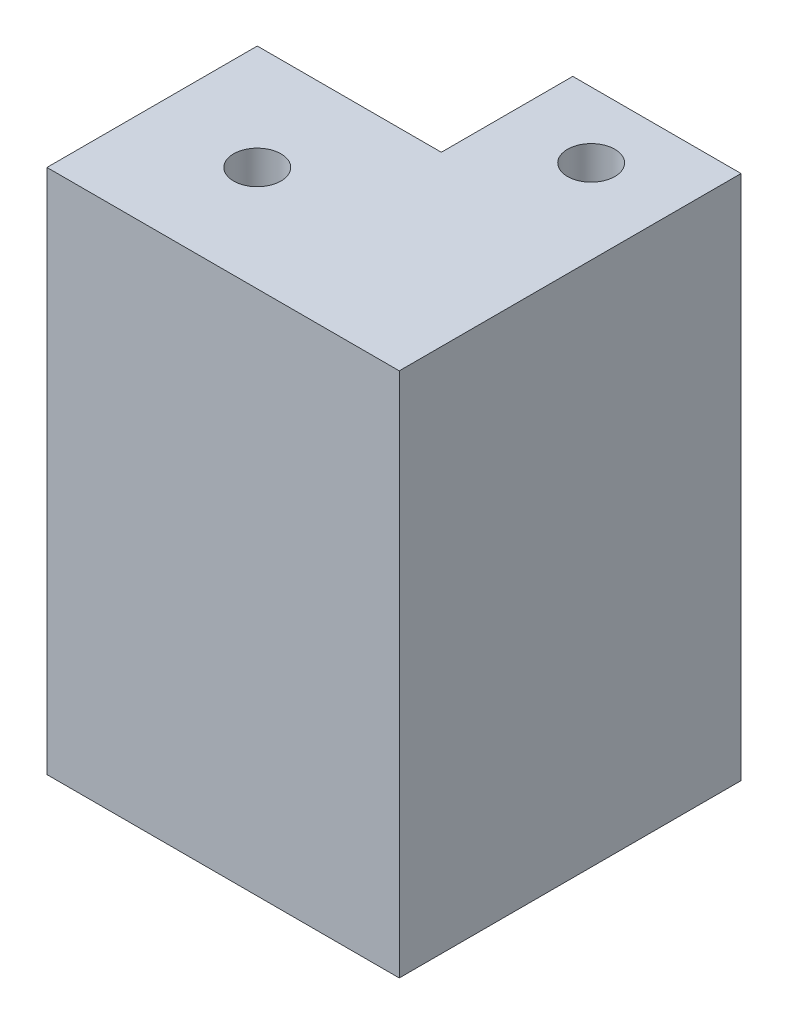
SolidWorks part; units mm, degrees
ref_plane "Front Plane" through (0, 0, 0) normal (0, 0, 1) x (1, 0, 0)
ref_plane "Top Plane" through (0, 0, 0) normal (0, 1, 0) x (1, 0, 0)
ref_plane "Right Plane" through (0, 0, 0) normal (1, 0, 0) x (0, 0, -1)
sketch "Sketch1" plane through (0, 0, 0) normal (0, 1, 0) x (1, 0, 0)
  line L19 (0, -40) -> (0, 0) construction
  line L24 (-25, 0) -> (-5, -40) construction
  line L25 (0, 25) -> (-25, 25) construction
  line L26 (-25, 25) -> (-25, 0) construction
  line L27 (0, 25) -> (32, 0) construction
  line L28 (32, 0) -> (0, 0) construction
  line L29 (-35, 0) -> (0, 0)
  line L30 (-35, -40) -> (-35, 0)
  line L31 (32, -40) -> (-35, -40)
  line L32 (32, 25) -> (32, -40)
  line L33 (0, 25) -> (32, 25)
  line L34 (0, 0) -> (0, 25)
  line L35 (-5, 5) -> (-5, -40) construction
  line L36 (-25, 25) -> (-5, 25) construction
  line L37 (-25, 25) -> (-25, 5) construction
  line L38 (-25, 5) -> (-5, 5) construction
  line L39 (-5, 25) -> (-5, 5) construction
  line L40 (16, 12.5) -> (-5, 22.5) construction
  line L41 (-25, 2.5) -> (-5, 2.5) construction
  line L42 (-25, 2.5) -> (-25, 22.5) construction
  line L43 (-25, 22.5) -> (-5, 22.5) construction
  line L44 (-5, 2.5) -> (-5, 22.5) construction
  line L45 (-25, 2.5) -> (-5, 22.5) construction
  line L46 (-25, 22.5) -> (-5, 2.5) construction
  line L47 (16, 12.5) -> (-5, 2.5) construction
  circle A10 centre (-15, -20) radius 16 construction
  circle A11 centre (-15, -20) radius 6.75 construction
  circle A12 centre (16, 12.5) radius 6 construction
  circle A13 centre (16, 12.5) radius 11 construction
  circle A14 centre (-15, -20) radius 4.5
  circle A15 centre (16, 12.5) radius 4.5
  point P1 (-15, 12.5)
  dimension "D4" = 40
  dimension "D6" = 9
  dimension "D3" = 32
  dimension "D5" = 20
  dimension "D7" = 13.5
  dimension "D8" = 32
  dimension "D9" = 9
  dimension "D10" = 12
  dimension "D11" = 22
  dimension "D1" = 25
  dimension "D2" = 25
  dimension "D12" = 20
extrude "Boss-Extrude1" add sketch "Sketch1" along normal blind 100
sketch "Sketch4" plane through (0, 0, 0) normal (0, -1, 0) x (-1, 0, 0)
  point P0 (15, -20)
hole_wizard "CBORE for M5 Hex Head Bolt2" positions "Sketch4" profile "Sketch5" counterbore size "M5" standard "ANSI Metric"
sketch "Sketch5" plane through (-15, 0, 20) normal (1, 0, 0) x (0, 0, -1)
  line L0 (0, 0) -> (0, 23.85)
  line L1 (0, 23.85) -> (6.75, 23.85)
  line L2 (6.75, 23.85) -> (6.75, 5)
  line L3 (6.75, 5) -> (16, 5)
  line L4 (16, 5) -> (16, 0)
  line L5 (16, 0) -> (0, 0)
  line L10 (0, 23.85) -> (-6.75, 23.85) construction
  line L11 (0, -6.35) -> (0, 107.95) construction
  dimension "Hole Dia." = 13.5
  dimension "Hole Depth" = 23.85
  dimension "C'Bore Dia." = 32
  dimension "C'Bore Depth" = 5
  dimension "Drill Angle" = 180
sketch "Sketch6" plane through (0, 0, 0) normal (0, -1, 0) x (-1, 0, 0)
  point P0 (-16, 12.5)
hole_wizard "CBORE for M5 Hex Head Bolt3" positions "Sketch6" profile "Sketch7" counterbore size "M5" standard "ANSI Metric"
sketch "Sketch7" plane through (16, 0, -12.5) normal (1, 0, 0) x (0, 0, -1)
  line L0 (0, 0) -> (0, 13.5)
  line L1 (0, 13.5) -> (5.1, 13.5)
  line L2 (5.1, 13.5) -> (5.1, 3.5)
  line L3 (5.1, 3.5) -> (11, 3.5)
  line L4 (11, 3.5) -> (11, 0)
  line L5 (11, 0) -> (0, 0)
  line L10 (0, 13.5) -> (-5.1, 13.5) construction
  line L11 (0, -6.35) -> (0, 107.95) construction
  dimension "Hole Dia." = 10.2
  dimension "Hole Depth" = 13.5
  dimension "C'Bore Dia." = 22
  dimension "C'Bore Depth" = 3.5
  dimension "Drill Angle" = 180
